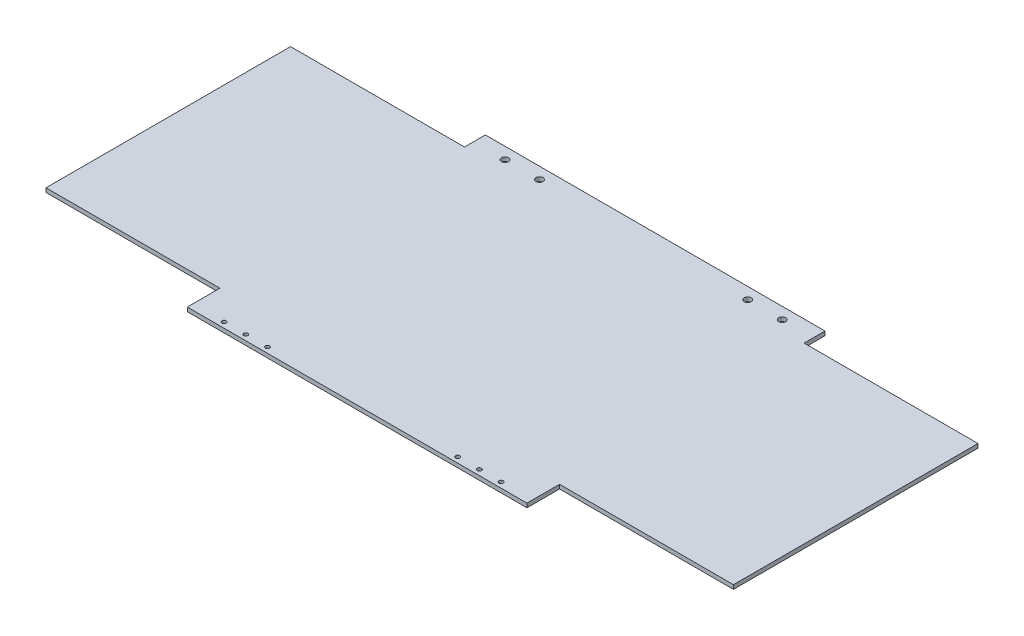
SolidWorks part; units mm, degrees
ref_plane "Front Plane" through (0, 0, 0) normal (0, 0, 1) x (1, 0, 0)
ref_plane "Top Plane" through (0, 0, 0) normal (0, 1, 0) x (1, 0, 0)
ref_plane "Right Plane" through (0, 0, 0) normal (1, 0, 0) x (0, 0, -1)
sketch "Sketch1" plane through (0, 0, 0) normal (0, 1, 0) x (1, 0, 0)
  line L0 (128, 0) -> (128, -24)
  line L1 (0, 0) -> (128, 0)
  line L2 (0, 0) -> (0, 180)
  line L3 (0, 180) -> (128, 180)
  line L4 (506, 0) -> (506, 180)
  line L5 (128, -24) -> (378, -24)
  line L6 (378, -24) -> (378, 0)
  line L7 (0, 90) -> (506, 90) construction
  line L8 (128, 180) -> (128, 195.398)
  line L9 (128, 195.398) -> (378, 195.398)
  line L10 (378, 195.398) -> (378, 180)
  line L11 (253, 195.398) -> (253, -38.1) construction
  line L12 (378, 0) -> (506, 0)
  line L13 (378, 180) -> (506, 180)
  line L14 (128, 186.858) -> (378, 186.858) construction
  line L15 (128, -20) -> (253, -20) construction
  circle A0 centre (151, 186.858) radius 2.564
  circle A1 centre (176.4, 186.858) radius 2.564
  circle A4 centre (151, -20) radius 1.54
  circle A5 centre (183, -20) radius 1.54
  circle A8 centre (329.6, 186.858) radius 2.564
  circle A9 centre (355, 186.858) radius 2.564
  circle A10 centre (167, -20) radius 1.54
  circle A11 centre (323, -20) radius 1.54
  circle A12 centre (339, -20) radius 1.54
  circle A13 centre (355, -20) radius 1.54
  point P10 (253, 90)
  dimension "D7" = 3.08
  dimension "D9" = 5.128
  dimension "D1" = 180
  dimension "D2" = 506
  dimension "D3" = 250
  dimension "D5" = 250
  dimension "D8" = 8.54
  dimension "D10" = 25.4
  dimension "D11" = 23
  dimension "D6" = 6.858
  dimension "D12" = 16
  dimension "D13" = 16
  dimension "D14" = 23
  dimension "D15" = 4
  dimension "D4" = 20
extrude "Boss-Extrude1" add sketch "Sketch1" along normal blind 3
equation "\"cf_tube_outer_diameter\"= 25mm"
equation "\"cf_tube_inner_diameter\"= 21mm"
equation "\"mid_plate_mid_to_top\"= 100mm"
equation "\"mid_plate_mid_to_bottom\"= 30mm"
equation "\"mid_plate_horizontal_spacing\"= 250mm"
equation "\"cf_plate_thickness\"= 3mm"
equation "\"mid_tube_length\"= 500mm"
equation "\"mid_plate_bottom_width\"= 180mm"
equation "\"D1@Sketch1\"=\"mid_plate_bottom_width\""
equation "\"D2@Sketch1\"=\"mid_tube_length\"+\"cf_plate_thickness\"*2"
equation "\"D1@Boss-Extrude1\"=\"cf_plate_thickness\""
equation "\"D5@Sketch1\"=\"mid_plate_horizontal_spacing\""
equation "\"D3@Sketch1\"=\"mid_plate_horizontal_spacing\""
